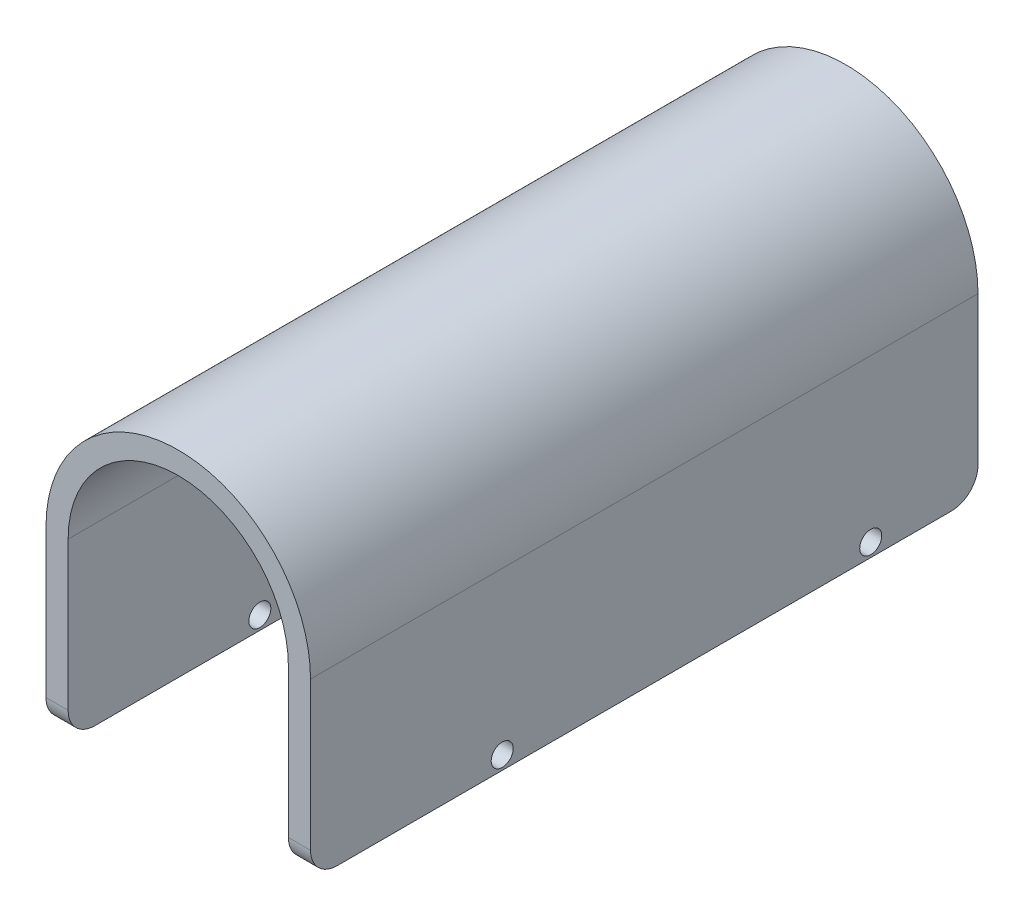
SolidWorks part; units mm, degrees
ref_plane "Piano frontale" through (0, 0, 0) normal (0, 0, 1) x (1, 0, 0)
ref_plane "Piano superiore" through (0, 0, 0) normal (0, 1, 0) x (1, 0, 0)
ref_plane "Piano destro" through (0, 0, 0) normal (1, 0, 0) x (0, 0, -1)
sketch "Schizzo1" plane through (0, 0, 0) normal (0, 0, 1) x (1, 0, 0)
  line L3 (-39.628, 0) -> (-33, 0)
  line L4 (33, 0) -> (39.628, 0)
  arc A4 (33, 0) -> (-33, 0) centre (0, 0) ccw
  arc A5 (39.628, 0) -> (-39.628, 0) centre (0, 0) ccw
extrude "Estrusione-Estrusione2" add sketch "Schizzo1" along normal blind 200
sketch "Schizzo2" plane through (0, 0, 0) normal (0, 0, 1) x (1, 0, 0)
  line L0 (-39.628, 0) -> (-39.628, -16.4293)
  line L1 (-33, 0) -> (-33, -16.4293)
  line L3 (33, 0) -> (33, -20)
  line L5 (39.628, -16.4293) -> (39.628, 0)
  line L6 (39.628, 0) -> (33, 0)
  line L7 (-39.628, 0) -> (-33, 0)
  line L8 (-39.628, -16.4293) -> (-39.628, -52.4293)
  line L9 (-39.628, -52.4293) -> (-33, -52.4293)
  line L10 (-33, -52.4293) -> (-33, -16.4293)
  line L11 (33, -20) -> (33, -52.4293)
  line L12 (33, -52.4293) -> (39.628, -52.4293)
  line L13 (39.628, -52.4293) -> (39.628, -16.4293)
  dimension "D1" = 36
  dimension "D2" = 36
extrude "Estrusione-Estrusione3" add sketch "Schizzo2" along normal up to vertex (200 mm away) up to point (-39.628, 0, 200)
fillet "Raccordo1" radius 8 4 edges at (36.314, -52.4293, 0) (-36.314, -52.4293, 0) (-36.314, -52.4293, 200) (36.314, -52.4293, 200)
sketch "Schizzo3" plane through (-39.628, 0, 0) normal (-1, 0, 0) x (0, 0, 1)
  line L0 (0, -48.3611) -> (32.14, -48.3611)
  line L2 (0, 0) -> (0, -44.4293) construction
  line L3 (32.14, -48.3611) -> (142.56, -48.3611)
  line L4 (0, -38.3649) -> (32.14, -38.3649)
  line L5 (32.14, -38.3649) -> (142.56, -38.3649)
hole_wizard "Foro filettato G1/16-4" positions "Schizzo10" profile "Schizzo11" tap size "G1/16" standard "GB" end condition through all
sketch "Schizzo10" plane through (-39.628, 0, 0) normal (-1, 0, 0) x (0, 0, 1)
  point P0 (32.14, -48.3611)
  point P3 (142.56, -48.3611)
sketch "Schizzo11" plane through (-39.628, -48.3611, 32.14) normal (0, 1, 0) x (0, 0, 1)
  line L0 (0, 0) -> (0, 79.2561)
  line L1 (0, 79.2561) -> (3.3, 79.2561)
  line L2 (3.3, 79.2561) -> (3.3, 0.5865)
  line L3 (3.3, 0.5865) -> (3.8865, 0)
  line L5 (3.8865, 0) -> (0, 0)
  line L6 (-3.3, 0.5865) -> (-3.8865, 0) construction
  line L11 (0, -6.35) -> (0, 107.95) construction
  dimension "Thru Tap Drill Dia." = 6.6
  dimension "Thru Tap Drill Depth" = 79.2561
  dimension "Near C'Sink Dia." = 7.773
  dimension "Near C'Sink Angle" = 90
cosmetic thread "Filettatura del foro7" parameters "D2"=7.723
cosmetic thread "Filettatura del foro8" parameters "D2"=7.723
